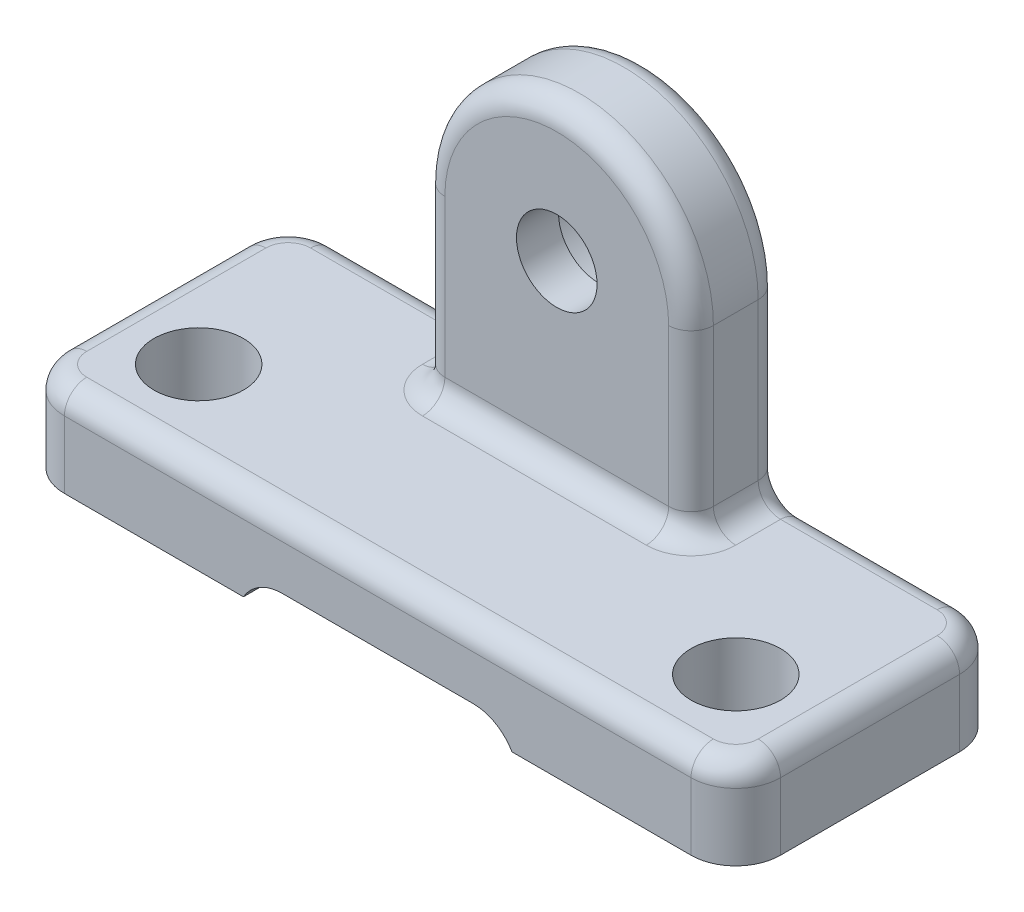
SolidWorks part; units mm, degrees
material "Brass"
ref_plane "Front Plane" through (0, 0, 0) normal (0, 0, 1) x (1, 0, 0)
ref_plane "Top Plane" through (0, 0, 0) normal (0, 1, 0) x (1, 0, 0)
ref_plane "Right Plane" through (0, 0, 0) normal (1, 0, 0) x (0, 0, -1)
sketch "Sketch1" plane through (0, 0, 0) normal (0, 1, 0) x (1, 0, 0)
  line L1 (-40, -15) -> (40, -15)
  line L2 (-40, -15) -> (-40, 15)
  line L3 (-40, 15) -> (40, 15)
  line L4 (40, -15) -> (40, 15)
  line L5 (-40, -15) -> (40, 15) construction
  line L6 (-40, 15) -> (40, -15) construction
  point P0 (0, 0)
  dimension "D1" = 30
  dimension "D2" = 80
extrude "Boss-Extrude1" add sketch "Sketch1" along normal blind 10
sketch "Sketch2" plane through (0, 0, -15) normal (0, 0, -1) x (-1, 0, 0)
  line L0 (0, 30) -> (15, 30)
  line L1 (15, 0) -> (-15, 0)
  line L2 (0, 0) -> (0, 30)
  line L3 (0, 30) -> (-15, 30)
  line L4 (-15, 0) -> (-15, 30)
  line L5 (15, 0) -> (15, 30)
  dimension "D1" = 30
  dimension "D2" = 30
extrude "Boss-Extrude2" add sketch "Sketch2" against normal blind 10 contours L0 L5 L1 L4 L3
sketch "Sketch4" plane through (0, 0, -15) normal (0, 0, -1) x (-1, 0, 0)
  line L0 (-15, 30) -> (15, 30) construction
  circle A0 centre (0, 30) radius 15
extrude "Boss-Extrude3" add sketch "Sketch4" against normal up to surface (10 mm away) up to face at (0, 20, -5)
hole_wizard "CBORE for M5 Hex Head Bolt1" positions "Sketch5" profile "Sketch6" counterbore size "M5" standard "ANSI Metric" end condition up to next
sketch "Sketch5" plane through (0, 0, -15) normal (0, 0, -1) x (-1, 0, 0)
  point P0 (0, 30)
sketch "Sketch6" plane through (0, 30, -15) normal (1, 0, 0) x (0, 1, 0)
  line L0 (0, 0) -> (0, 10)
  line L1 (0, 10) -> (4.5, 10)
  line L3 (4.5, 10) -> (4.5, 5.3)
  line L4 (4.5, 5.3) -> (9.005, 5.3)
  line L5 (9.005, 5.3) -> (9.005, 0)
  line L7 (9.005, 0) -> (0, 0)
  line L11 (0, -6.35) -> (0, 107.95) construction
  dimension "Thru Hole Dia." = 9
  dimension "Thru Hole Depth" = 10
  dimension "C'Bore Dia." = 18.01
  dimension "C'Bore Depth" = 5.3
sketch "Sketch7" plane through (0, 0, 15) normal (0, 0, 1) x (1, 0, 0)
  line L0 (-15, 0) -> (15, 0)
  line L1 (-40, 0) -> (40, 0) construction
  line L2 (15, 0) -> (15, 2.5)
  line L3 (15, 2.5) -> (-15, 2.5)
  line L4 (-15, 2.5) -> (-15, 0)
  dimension "D1" = 2.5
extrude "Cut-Extrude1" cut sketch "Sketch7" against normal up to next
sketch "Sketch8" plane through (0, 10, 0) normal (0, 1, 0) x (1, 0, 0)
  line L0 (-40, -15) -> (40, -15) construction
  line L1 (-40, 15) -> (-40, -15) construction
  line L2 (40, -15) -> (40, 15) construction
  circle A0 centre (-30, -5) radius 5
  circle A1 centre (30, -5) radius 5
  dimension "D1" = 10
  dimension "D2" = 10
  dimension "D3" = 10
  dimension "D4" = 10
  dimension "D5" = 10
  dimension "D6" = 10
extrude "Cut-Extrude2" cut sketch "Sketch8" against normal up to next
fillet "Fillet1" radius 5 6 edges at (15, 2.5, 0) (-15, 2.5, 0) (-40, 5, -15) (-40, 5, 15) (40, 5, -15) (40, 5, 15)
fillet "Fillet2" radius 2.5 18 edges at (-15, 10, -10) (0, 10, -5) (-15, 20, -5) (0, 45, -5) (-15, 20, -15) (0, 45, -15) (-25, 10, -15) (-38.5355, 10, -13.5355) (-40, 10, 0) (-38.5355, 10, 13.5355) (0, 10, 15) (38.5355, 10, 13.5355) (25, 10, -15) (38.5355, 10, -13.5355) (15, 10, -10) (15, 20, -5) (15, 20, -15) (40, 10, 0)
